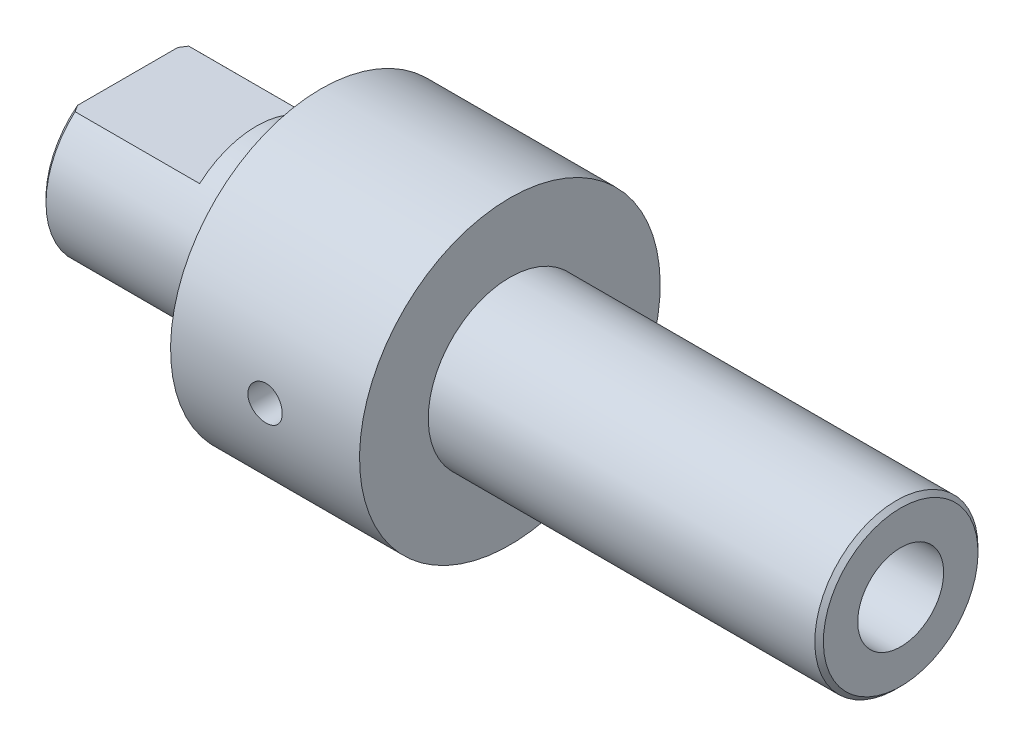
SolidWorks part; units mm, degrees
material "Титан Ti-5Al-2.5Sn"
ref_plane "Спереди" through (0, 0, 0) normal (0, 0, 1) x (1, 0, 0)
ref_plane "Сверху" through (0, 0, 0) normal (0, 1, 0) x (1, 0, 0)
ref_plane "Справа" through (0, 0, 0) normal (1, 0, 0) x (0, 0, -1)
sketch "Эскиз2" plane through (0, 0, 0) normal (0, 0, 1) x (1, 0, 0)
  line L0 (0, 0) -> (0, 38)
  line L1 (0, 0) -> (-90.9972, 0)
  line L2 (0, 38) -> (-90.9972, 38)
  line L3 (-179.9972, -1) -> (-179.9972, 39)
  line L4 (-134.9972, -16) -> (-90.9972, -16)
  line L5 (-134.9972, -16) -> (-134.9972, 54)
  line L6 (-90.9972, -16) -> (-90.9972, 54)
  line L7 (-134.9972, 54) -> (-90.9972, 54)
  line L8 (-15, 25) -> (-15, 13)
  line L9 (-90.9972, 38) -> (-15, 38)
  line L10 (-15, 25) -> (-55, 25)
  line L11 (-15, 13) -> (-55, 13)
  line L12 (-55, 25) -> (-55, 13)
  line L16 (-134.9972, 39) -> (-179.9972, 39)
  line L17 (-134.9972, -1) -> (-179.9972, -1)
  line L18 (0, 19) -> (-288.7166, 19) construction
  line L19 (-179.9972, 19) -> (0, 19)
  line L25 (-112.9972, 54) -> (-112.9972, -16) construction
  circle A0 centre (-112.9972, 19) radius 4
  dimension "D4" = 8
  dimension "D1" = 180
  dimension "D2" = 38
  dimension "D3" = 20
  dimension "D5" = 15
  dimension "D6" = 44
  dimension "D7" = 40
  dimension "D8" = 15
  dimension "D9" = 40
  dimension "D10" = 12
  dimension "D11" = 6
  dimension "D13" = 70
  dimension "D14" = 35
  dimension "D15" = 45
revolve "Повернуть3" add sketch "Эскиз2" angle 360 about L18 region at (-47.1909, 29.5477, 0) region at (-112.9972, 36.7622, 0) region at (-157.4972, 29, 0)
sketch "Эскиз6" plane through (0, 0, 0) normal (1, 0, 0) x (0, 0, -1)
  circle A0 centre (0, 19) radius 10
  dimension "D1" = 20
extrude "Вырез-Вытянуть4" cut sketch "Эскиз6" against normal through all
extrude "Вырез-Вытянуть5" cut sketch "Эскиз2<9>" against normal through all both and the other way through all contours A0
sketch "Эскиз2<9>" plane through (0, 0, 0) normal (0, 0, 1) x (1, 0, 0) same geometry as "Эскиз2"
chamfer "Фаска2" distance 1 angle 45 2 edges at (0, 38, 0) (-179.9972, 39, 0)
sketch "Эскиз7" plane through (-179.9972, 0, 0) normal (-1, 0, 0) x (0, 0, 1)
  line L0 (22.728, 4) -> (22.728, -8)
  line L1 (22.728, -8) -> (-22.272, -8)
  line L2 (22.728, 4) -> (-22.272, 4)
  line L3 (-22.272, -8) -> (-22.272, 4)
  line L4 (22.728, 34) -> (-22.272, 34)
  line L5 (22.728, 34) -> (22.728, 46)
  line L6 (22.728, 46) -> (-22.272, 46)
  line L7 (-22.272, 46) -> (-22.272, 34)
  line L8 (0, 9) -> (0, 29) construction
  line L9 (0, 19) -> (19, 19) construction
  circle A0 centre (0, 19) radius 10 construction
  circle A1 centre (0, 19) radius 19 construction
  dimension "D1" = 30
  dimension "D2" = 15
  dimension "D3" = 45
  dimension "D4" = 45
  dimension "D5" = 26.8522
  dimension "D6" = 27.2316
  dimension "D7" = 12
  dimension "D8" = 12
extrude "Вырез-Вытянуть6" cut sketch "Эскиз7" against normal blind 30
sketch "Эскиз8" plane through (0, 0, 0) normal (1, 0, 0) x (0, 0, -1)
  line L0 (-14, -3.3293) -> (-14, 39.8683)
  line L1 (-14, -3.3293) -> (-22.7796, -3.3293)
  line L2 (-14, 39.8683) -> (-22.7796, 39.8683)
  line L3 (-22.7796, -3.3293) -> (-22.7796, 39.8683)
  circle A0 centre (0, 19) radius 18 construction
  dimension "D1" = 14
  dimension "D2" = 8.7796
  dimension "D3" = 43.1976
  dimension "D4" = 14.3904
extrude "Вырез-Вытянуть8" cut sketch "Эскиз2<10>" against normal blind 40 from offset 14 contours L11 L12 L10 L8 offset against normal yes
sketch "Эскиз2<10>" plane through (0, 0, 0) normal (0, 0, 1) x (1, 0, 0) same geometry as "Эскиз2"
